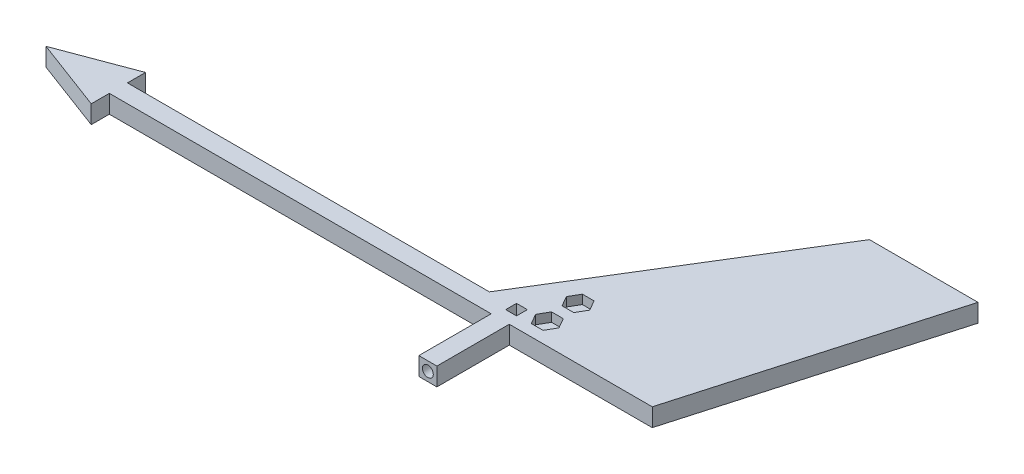
SolidWorks part; units mm, degrees
ref_plane "Front Plane" through (0, 0, 0) normal (0, 0, 1) x (1, 0, 0)
ref_plane "Top Plane" through (0, 0, 0) normal (0, 1, 0) x (1, 0, 0)
ref_plane "Right Plane" through (0, 0, 0) normal (1, 0, 0) x (0, 0, -1)
other "Center of Mass"
sketch "Sketch1" plane through (0, 0, 0) normal (0, 1, 0) x (1, 0, 0)
  line L0 (-20, 0) -> (0, 7.5)
  line L1 (-20, 0) -> (0, -7.5)
  line L2 (0, -7.5) -> (0, 7.5) construction
  line L3 (0, 7.5) -> (0, 2.5)
  line L4 (0, 2.5) -> (100, 2.5)
  line L5 (0, -7.5) -> (0, -2.5)
  line L6 (0, -2.5) -> (150, -2.5)
  line L7 (150, -2.5) -> (170, 67.5)
  line L8 (170, 67.5) -> (140, 67.5)
  line L9 (140, 67.5) -> (100, 2.5)
  point P2 (0, 0)
  dimension "D1" = 150
  dimension "D2" = 100
  dimension "D3" = 70
  dimension "D4" = 20
  dimension "D5" = 40
  dimension "D6" = 20
  dimension "D7" = 15
  dimension "D8" = 5
extrude "Boss-Extrude1" add sketch "Sketch1" along normal mid plane 5
sketch "Sketch2" plane through (0, 2.5, 0) normal (0, 1, 0) x (1, 0, 0)
  line L0 (118.2332, 12) -> (116.6166, 14.8)
  line L2 (116.6166, 14.8) -> (113.3834, 14.8)
  line L5 (113.3834, 9.2) -> (116.6166, 9.2)
  line L6 (116.6166, 9.2) -> (118.2332, 12)
  line L8 (113.3834, 14.8) -> (111.7668, 12)
  line L9 (111.7668, 12) -> (113.3834, 9.2)
  line L12 (0, -2.5) -> (150, -2.5) construction
  line L13 (118.2332, 3.5) -> (116.6166, 6.3)
  line L14 (116.6166, 6.3) -> (113.3834, 6.3)
  line L15 (113.3834, 6.3) -> (111.7668, 3.5)
  line L16 (111.7668, 3.5) -> (113.3834, 0.7)
  line L17 (113.3834, 0.7) -> (116.6166, 0.7)
  line L18 (116.6166, 0.7) -> (118.2332, 3.5)
  line L19 (118.2332, 12) -> (116.6166, 14.8) [skipped]
  line L20 (113.3834, 14.8) -> (111.7668, 12) [skipped]
  line L21 (111.7668, 12) -> (113.3834, 9.2) [skipped]
  circle A0 centre (115, 12) radius 2.8 construction
  circle A1 centre (115, 12) radius 2.8 construction
  circle A2 centre (115, 3.5) radius 2.8 construction
  dimension "D3" = 6
  dimension "D6" = 5.6
  dimension "D5" = 8.5
  dimension "D7" = 15
extrude "Cut-Extrude2" cut sketch "Sketch2" against normal blind 2.5
sketch "Sketch3" plane through (0, 0, 2.5) normal (0, 0, 1) x (1, 0, 0)
  line L1 (105.5, -2.5) -> (110.5, -2.5)
  line L2 (105.5, -2.5) -> (105.5, 2.5)
  line L3 (105.5, 2.5) -> (110.5, 2.5)
  line L4 (110.5, -2.5) -> (110.5, 2.5)
  line L5 (105.5, -2.5) -> (110.5, 2.5) construction
  line L6 (105.5, 2.5) -> (110.5, -2.5) construction
  line L7 (0, 2.5) -> (150, 2.5) construction
  line L8 (0, -2.5) -> (150, -2.5) construction
  point P0 (108, 0)
  dimension "D1" = 5
  dimension "D2" = 108
extrude "Boss-Extrude2" add sketch "Sketch3" along normal blind 20
sketch "Sketch4" plane through (0, 0, 22.5) normal (0, 0, 1) x (1, 0, 0)
  line L0 (105.5, 0) -> (110.5, 0) construction
  line L1 (105.5, 2.5) -> (105.5, -2.5) construction
  line L2 (110.5, -2.5) -> (110.5, 2.5) construction
  circle A0 centre (108, 0) radius 1.5
  dimension "D1" = 3
extrude "Cut-Extrude3" cut sketch "Sketch4" against normal blind 23
sketch "Sketch6" plane through (0, 2.5, 0) normal (0, 1, 0) x (1, 0, 0)
  line L0 (105.5, -2.5) -> (110.5, -2.5) construction
  line L1 (106.5, 0.5) -> (109.5, 0.5)
  line L2 (106.5, 0.5) -> (106.5, 3.5)
  line L3 (106.5, 3.5) -> (109.5, 3.5)
  line L4 (109.5, 0.5) -> (109.5, 3.5)
  line L5 (106.5, 0.5) -> (109.5, 3.5) construction
  line L6 (106.5, 3.5) -> (109.5, 0.5) construction
  point P0 (108, 2)
  point P5 (108, -2.5)
  dimension "D1" = 3
  dimension "D2" = 3
  dimension "D3" = 3
extrude "Cut-Extrude5" cut sketch "Sketch6" against normal blind 4
